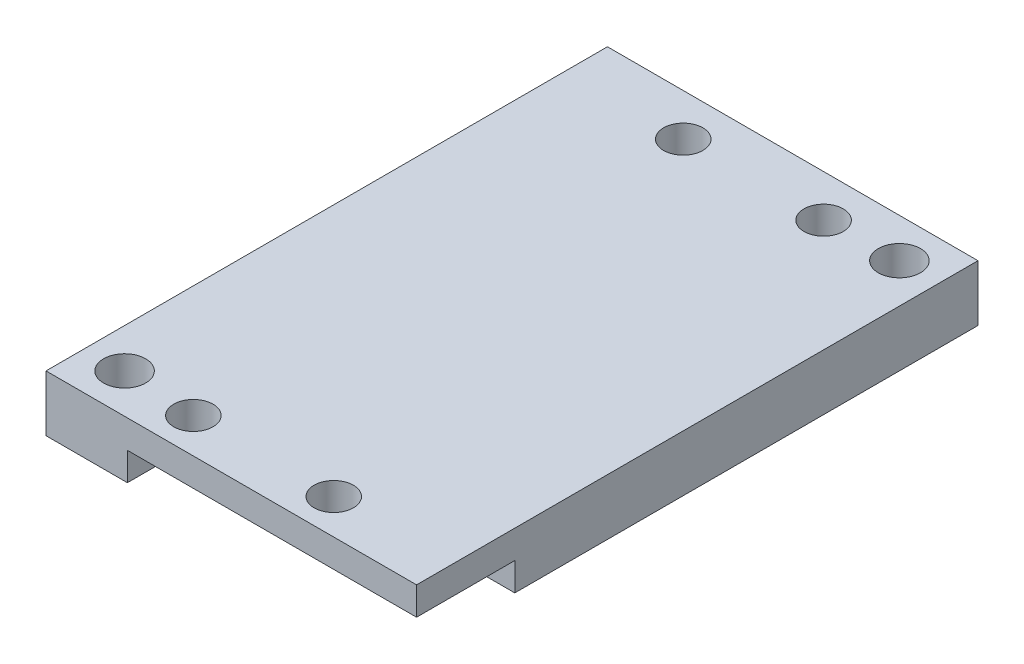
SolidWorks part; units mm, degrees
ref_plane "前视基准面" through (0, 0, 0) normal (0, 0, 1) x (1, 0, 0)
ref_plane "上视基准面" through (0, 0, 0) normal (0, 1, 0) x (1, 0, 0)
ref_plane "右视基准面" through (0, 0, 0) normal (1, 0, 0) x (0, 0, -1)
other "Configuration Table"
sketch "草图1" plane through (0, 0, 0) normal (0, 1, 0) x (1, 0, 0)
  line L1 (-6.6, 10) -> (6.6, 10)
  line L2 (-6.6, 10) -> (-6.6, -10)
  line L3 (-6.6, -10) -> (6.6, -10)
  line L4 (6.6, 10) -> (6.6, -10)
  line L5 (-6.6, 10) -> (6.6, -10) construction
  line L6 (-6.6, -10) -> (6.6, 10) construction
  circle A0 centre (-5.2, -8.6) radius 0.75
  circle A1 centre (5.2, 8.6) radius 0.75
  point P0 (0, 0)
  point P5 (3, -8.5)
  dimension "D7" = 1.5
  dimension "D1" = 20
  dimension "D2" = 13.2
  dimension "D3" = 1.4
  dimension "D4" = 1.4
  dimension "D5" = 1.4
  dimension "D6" = 1.4
extrude "凸台-拉伸1" add sketch "草图1" along normal blind 2 contours L2 L3 L4 L1
extrude "切除-拉伸2" cut sketch "草图1<3>" along normal through all contours A0 | A1
sketch "草图1<3>" plane through (0, 0, 0) normal (0, 1, 0) x (1, 0, 0) same geometry as "草图1"
sketch "草图2" plane through (0, 2, 0) normal (0, 1, 0) x (1, 0, 0)
  line L0 (6.6, 10) -> (6.6, -10) construction
  line L1 (-6.6, 10) -> (3.7, 10)
  line L2 (-6.6, 10) -> (-6.6, 6.5)
  line L3 (-6.6, 6.5) -> (3.7, 6.5)
  line L4 (3.7, 10) -> (3.7, 6.5)
  line L5 (6.6, -10) -> (-3.7, -10)
  line L6 (6.6, -10) -> (6.6, -6.5)
  line L7 (6.6, -6.5) -> (-3.7, -6.5)
  line L8 (-3.7, -10) -> (-3.7, -6.5)
  line L9 (-6.6, -10) -> (6.6, -10) construction
  line L10 (6.6, 10) -> (6.6, -10) construction
  line L11 (-6.6, 10) -> (-6.6, -10) construction
  circle A0 centre (-2.6, -8.75) radius 0.7
  circle A1 centre (2.4, -8.75) radius 0.7
  circle A2 centre (-2.4, 8.5) radius 0.7
  circle A3 centre (2.6, 8.5) radius 0.7
  point P23 (0, 0)
  point P24 (0, 0)
  point P25 (0, 0)
  dimension "D5" = 1.4
  dimension "D1" = 3.5
  dimension "D2" = 10.3
  dimension "D3" = 4
  dimension "D4" = 5
  dimension "D6" = 1.25
  dimension "D7" = 1.5
  dimension "D8" = 5
  dimension "D9" = 4
extrude "切除-拉伸1" cut sketch "草图2" along normal blind 1 from surface contours L1 L4 L3 L2 | L7 L8 L5 L6 starting at face at (-5.2, 0, 9.35)
extrude "切除-拉伸4" cut sketch "草图2<3>" against normal through all contours A0 | A1 | A2 | A3
sketch "草图2<3>" plane through (0, 2, 0) normal (0, 1, 0) x (1, 0, 0) same geometry as "草图2"
